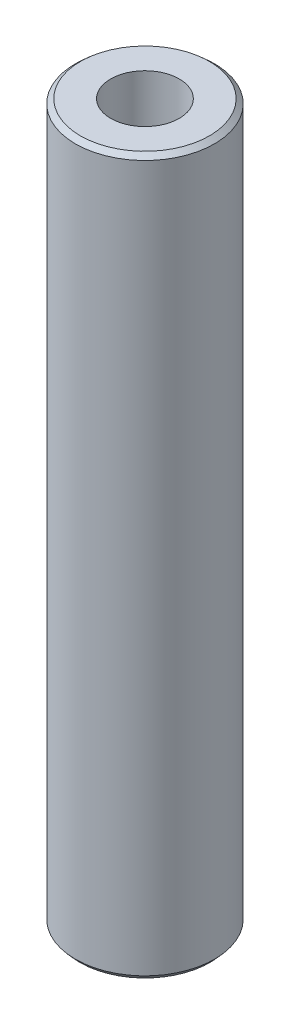
SolidWorks part; units mm, degrees
ref_plane "Front Plane" through (0, 0, 0) normal (0, 0, 1) x (1, 0, 0)
ref_plane "Top Plane" through (0, 0, 0) normal (0, 1, 0) x (1, 0, 0)
ref_plane "Right Plane" through (0, 0, 0) normal (1, 0, 0) x (0, 0, -1)
sketch "Sketch1" plane through (0, 0, 0) normal (0, 1, 0) x (1, 0, 0)
  circle A0 centre (0, 0) radius 37.5
  dimension "SHAFT_OD" = 75
extrude "Boss-Extrude1" add sketch "Sketch1" along normal blind 386.0965
sketch "Sketch2" plane through (0, 0, 0) normal (0, 1, 0) x (1, 0, 0)
  circle A0 centre (0, 0) radius 18.4799
  dimension "BORE_D" = 36.9597
extrude "Cut-Extrude1" cut sketch "Sketch2" along normal through all
chamfer "Chamfer1" distance 2.3885 angle 48.52 2 edges at (0, 386.0965, 37.5) (0, 0, 37.5) first distance on face at (0, 386.0965, 37.5) first distance on face at (0, 0, 18.4799)
